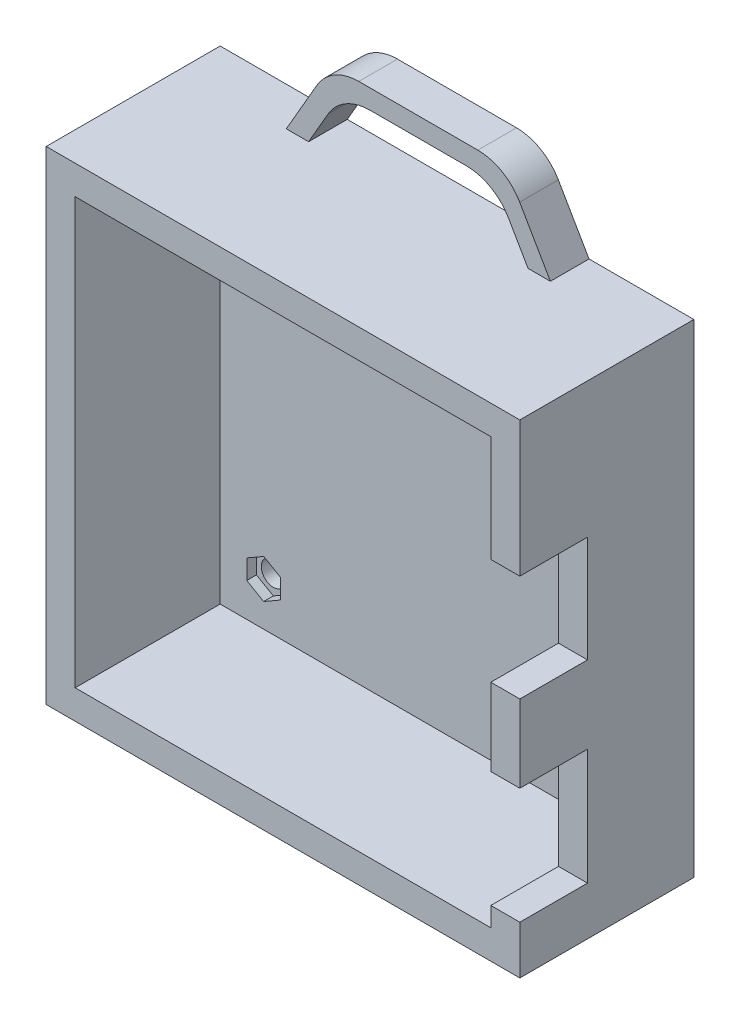
SolidWorks part; units mm, degrees
ref_plane "前视基准面" through (0, 0, 0) normal (0, 0, 1) x (1, 0, 0)
ref_plane "上视基准面" through (0, 0, 0) normal (0, 1, 0) x (1, 0, 0)
ref_plane "右视基准面" through (0, 0, 0) normal (1, 0, 0) x (0, 0, -1)
other "Configuration Table"
sketch "草图1" plane through (0, 0, 0) normal (0, 0, 1) x (1, 0, 0)
  line L1 (24.5, 25) -> (-24.5, 25)
  line L2 (24.5, 25) -> (24.5, -25)
  line L3 (24.5, -25) -> (-24.5, -25)
  line L4 (-24.5, 25) -> (-24.5, -25)
  line L5 (24.5, 25) -> (-24.5, -25) construction
  line L6 (24.5, -25) -> (-24.5, 25) construction
  point P0 (0, 0)
  dimension "D1" = 49
  dimension "D2" = 50
extrude "凸台-拉伸1" add sketch "草图1" along normal blind 10
sketch "草图3" plane through (0, 0, 10) normal (0, 0, 1) x (1, 0, 0)
  line L1 (21.5, 22) -> (-21.5, 22)
  line L2 (21.5, 22) -> (21.5, -22)
  line L3 (21.5, -22) -> (-21.5, -22)
  line L4 (-21.5, 22) -> (-21.5, -22)
  line L5 (21.5, 22) -> (-21.5, -22) construction
  line L6 (21.5, -22) -> (-21.5, 22) construction
  point P0 (0, 0)
  dimension "D1" = 43
  dimension "D2" = 44
extrude "切除-拉伸1" cut sketch "草图3" against normal blind 7
sketch "草图4" plane through (0, 0, 3) normal (0, 0, 1) x (1, 0, 0)
  line L0 (21.5, 22) -> (-21.5, 22) construction
  line L1 (17, 15.4793) -> (18.75, 16.4896)
  line L2 (18.75, 16.4896) -> (18.75, 18.5104)
  line L3 (18.75, 18.5104) -> (17, 19.5207)
  line L4 (17, 19.5207) -> (15.25, 18.5104)
  line L5 (15.25, 18.5104) -> (15.25, 16.4896)
  line L6 (15.25, 16.4896) -> (17, 15.4793)
  line L7 (21.5, -22) -> (21.5, 22) construction
  line L8 (21.5, -22) -> (21.5, 22) construction
  line L9 (-21.5, -22) -> (21.5, -22) construction
  line L10 (-17, -19.5207) -> (-15.25, -18.5104)
  line L11 (-15.25, -18.5104) -> (-15.25, -16.4896)
  line L12 (-15.25, -16.4896) -> (-17, -15.4793)
  line L13 (-17, -15.4793) -> (-18.75, -16.4896)
  line L14 (-18.75, -16.4896) -> (-18.75, -18.5104)
  line L15 (-18.75, -18.5104) -> (-17, -19.5207)
  line L16 (-21.5, 22) -> (-21.5, -22) construction
  line L20 (-21.5, 22) -> (-21.5, -22) construction
  circle A0 centre (17, 17.5) radius 1.75 construction
  circle A1 centre (-17, -17.5) radius 1.75 construction
  point P26 (-37.7474, -11.9312)
  point P31 (-31.7934, -13.8941)
  dimension "D1" = 3.5
  dimension "D2" = 4.5
  dimension "D3" = 4.5
  dimension "D4" = 4.5
  dimension "D5" = 4.5
  dimension "D6" = 3.5
extrude "切除-拉伸2" cut sketch "草图4" against normal blind 1
sketch "草图5" plane through (0, 0, 2) normal (0, 0, 1) x (1, 0, 0)
  line L0 (-18.75, -16.4896) -> (-15.25, -18.5104) construction
  line L1 (-15.25, -16.4896) -> (-18.75, -18.5104) construction
  line L2 (17, 19.5207) -> (17, 15.4793) construction
  line L3 (15.25, 18.5104) -> (18.75, 16.4896) construction
  circle A0 centre (-17, -17.5) radius 1.25
  circle A1 centre (17, 17.5) radius 1.25
  dimension "D1" = 2.5
  dimension "D2" = 2.5
extrude "切除-拉伸3" cut sketch "草图5" against normal blind 3
sketch "草图7" plane through (24.5, 0, 0) normal (1, 0, 0) x (0, 0, -1)
  line L0 (-10, 25) -> (0, 25) construction
  line L1 (-10, -25) -> (-18, -25)
  line L2 (-10, -25) -> (-10, 25)
  line L3 (-10, 25) -> (-18, 25)
  line L4 (-18, -25) -> (-18, 25)
  dimension "D1" = 8
extrude "凸台-拉伸2" add sketch "草图7" against normal blind 3
sketch "草图8" plane through (24.5, 0, 0) normal (1, 0, 0) x (0, 0, -1)
  line L0 (-18, 25) -> (-18, -25) construction
  line L1 (-18, -8) -> (-11, -8)
  line L2 (-18, -8) -> (-18, -20)
  line L3 (-18, -20) -> (-11, -20)
  line L4 (-11, -8) -> (-11, -20)
  line L5 (0, -25) -> (0, 25) construction
  line L6 (-18, 11) -> (-11, 11)
  line L7 (-18, 11) -> (-18, 0)
  line L8 (-18, 0) -> (-11, 0)
  line L9 (-11, 11) -> (-11, 0)
  line L10 (-18, -25) -> (0, -25) construction
  dimension "D1" = 11
  dimension "D2" = 5
  dimension "D3" = 12
  dimension "D4" = 25
  dimension "D5" = 11
  dimension "D6" = 11
extrude "切除-拉伸5" cut sketch "草图8" against normal blind 3
sketch "草图9" plane through (0, 0, 10) normal (0, 0, 1) x (1, 0, 0)
  line L8 (-24.5, -25) -> (21.5, -25)
  line L9 (21.5, -25) -> (21.5, -22)
  line L10 (21.5, -22) -> (-21.5, -22)
  line L11 (-21.5, -22) -> (-21.5, 22)
  line L12 (-21.5, 22) -> (21.5, 22)
  line L13 (21.5, 22) -> (21.5, 25)
  line L14 (21.5, 25) -> (-24.5, 25)
  line L15 (-24.5, 25) -> (-24.5, -25)
  line L16 (-24.5, -25) -> (21.5, -25)
  line L17 (21.5, -25) -> (21.5, -22)
  line L18 (21.5, -22) -> (-21.5, -22)
  line L19 (-21.5, -22) -> (-21.5, 22)
  line L20 (-21.5, 22) -> (21.5, 22)
  line L21 (21.5, 22) -> (21.5, 25)
  line L22 (21.5, 25) -> (-24.5, 25)
  line L23 (-24.5, 25) -> (-24.5, -25)
  dimension "D1" = 0
extrude "凸台-拉伸3" add sketch "草图9" along normal up to surface (8 mm away) up to face at (23, 18, 18)
ref_axis "基准轴1" through (0, 0, 0) along (0, 0, -1)
sketch "草图11" plane through (0, 0, 0) normal (0, 0, -1) x (-1, 0, 0)
  line L0 (0, 0) -> (-41.3504, 0) construction
  line L12 (-13.6603, -25) -> (-11.3509, -25)
  line L13 (11.3509, -25) -> (13.6603, -25)
  line L18 (0, 0) -> (0, -43.3879) construction
  line L19 (-11.3509, -25) -> (-9.3301, -28.5)
  line L20 (24.5, -25) -> (-24.5, -25) construction
  line L21 (-5, -31) -> (5, -31)
  line L22 (9.3301, -28.5) -> (11.3509, -25)
  line L23 (-13.0829, -26) -> (-10.4848, -30.5)
  line L24 (-6.1547, -33) -> (6.1547, -33)
  line L25 (10.4848, -30.5) -> (13.0829, -26)
  line L26 (-13.0829, -26) -> (-13.6603, -25)
  line L27 (13.0829, -26) -> (13.6603, -25)
  line L28 (-9.0415, -33) -> (9.0415, -33) construction
  line L29 (9.0415, -33) -> (13.0829, -26) construction
  line L30 (-7.8868, -31) -> (7.8868, -31) construction
  line L31 (7.8868, -31) -> (11.3509, -25) construction
  line L32 (-13.0829, -26) -> (-9.0415, -33) construction
  line L33 (-11.3509, -25) -> (-7.8868, -31) construction
  arc A4 (6.1547, -33) -> (10.4848, -30.5) centre (6.1547, -28) ccw
  arc A5 (5, -31) -> (9.3301, -28.5) centre (5, -26) ccw
  arc A6 (-10.4848, -30.5) -> (-6.1547, -33) centre (-6.1547, -28) ccw
  arc A7 (-9.3301, -28.5) -> (-5, -31) centre (-5, -26) ccw
  dimension "D8" = 5
  dimension "D6" = 2
  dimension "D7" = 6
  dimension "D9" = 10
  dimension "D10" = 60
extrude "凸台-拉伸4" add sketch "草图11" against normal blind 4
mirror "镜向1" about plane through (0, 0, 0) normal (0, 1, 0) of "凸台-拉伸4"
